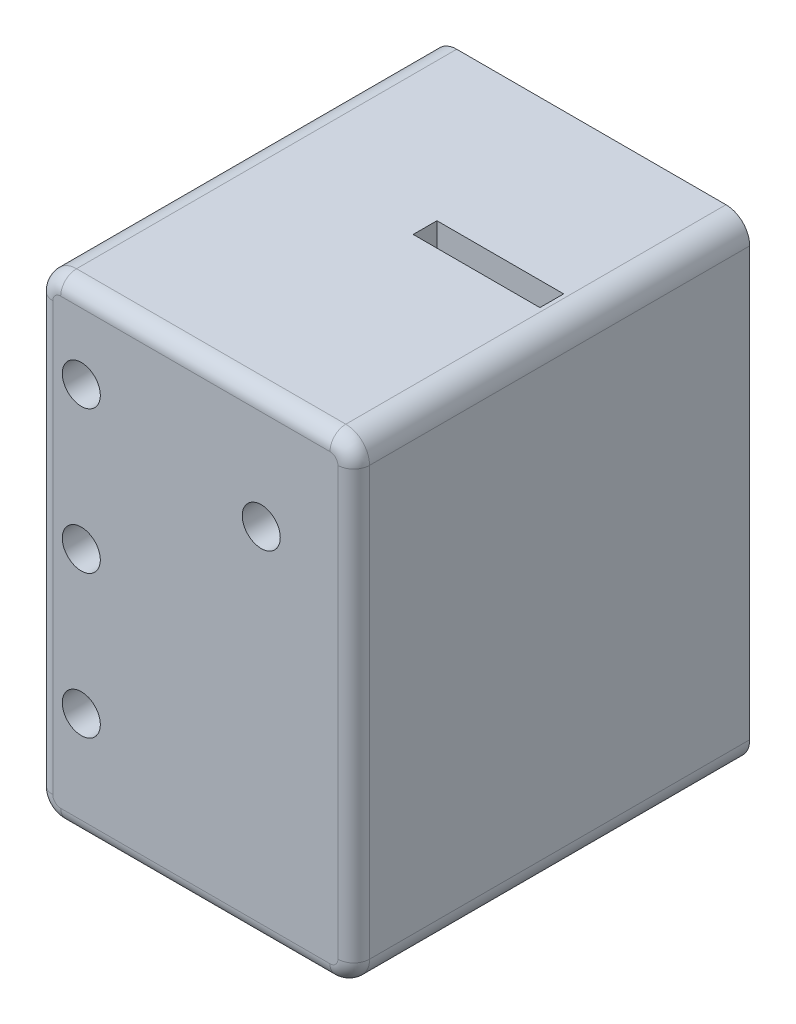
SolidWorks part; units mm, degrees
ref_plane "Front Plane" through (0, 0, 0) normal (0, 0, 1) x (1, 0, 0)
ref_plane "Top Plane" through (0, 0, 0) normal (0, 1, 0) x (1, 0, 0)
ref_plane "Right Plane" through (0, 0, 0) normal (1, 0, 0) x (0, 0, -1)
sketch "Sketch1" plane through (0, 0, 0) normal (0, 0, 1) x (1, 0, 0)
  line L0 (0, 0) -> (0, -30)
  line L1 (0, 0) -> (20, 0)
  line L2 (20, 0) -> (20, -30)
  line L3 (20, -30) -> (0, -30)
extrude "Boss-Extrude1" add sketch "Sketch1" along normal blind 25
sketch "Sketch4" plane through (0, -30, 0) normal (0, -1, 0) x (1, 0, 0)
  line L3 (18.2519, 10) -> (18.2519, 11.5)
  line L4 (18.2519, 11.5) -> (10.2519, 11.5)
  line L5 (10.2519, 11.5) -> (10.2519, 10)
  line L6 (10.2519, 10) -> (18.2519, 10)
extrude "Cut-Extrude2" cut sketch "Sketch4" against normal through all both and the other way through all contours L4 L5 L6 L3
sketch "Sketch5" plane through (0, 0, 0) normal (0, 1, 0) x (1, 0, 0)
  line L0 (18.2519, -11.5) -> (18.2519, -23)
  line L1 (18.2519, -23) -> (10.2519, -23)
  line L2 (10.2519, -23) -> (10.2519, -11.5)
  line L3 (18.2519, -11.5) -> (10.2519, -11.5) construction
  line L4 (10.2519, -11.5) -> (18.2519, -11.5)
extrude "Cut-Extrude3" cut sketch "Sketch5" against normal blind 15
sketch "Sketch6" plane through (0, -30, 0) normal (0, -1, 0) x (1, 0, 0)
  line L0 (10.2519, 10) -> (3.5878, 10)
  line L1 (3.5878, 10) -> (3.5878, 23)
  line L2 (3.5878, 23) -> (10.2519, 23)
  line L3 (10.2519, 11.5) -> (10.2519, 23) construction
  line L4 (10.2519, 23) -> (10.2519, 10)
extrude "Cut-Extrude4" cut sketch "Sketch6" against normal blind 28
sketch "Sketch7" plane through (0, 0, 10) normal (0, 0, 1) x (1, 0, 0)
  line L1 (18.2519, -15) -> (18.2519, 0) construction
  line L2 (18.2519, -12) -> (10.2519, -12)
  line L3 (10.2519, -12) -> (10.2519, -3)
  line L4 (10.2519, -3) -> (18.2519, -3)
  line L5 (18.2519, -12) -> (18.2519, -3)
extrude "Cut-Extrude5" cut sketch "Sketch7" against normal blind 3
sketch "Sketch11" plane through (0, 0, 10) normal (0, 0, 1) x (1, 0, 0)
  line L0 (10.2519, -15) -> (10.2519, -30) construction
  line L1 (3.5878, -30) -> (10.2519, -30)
  line L2 (3.5878, -30) -> (3.5878, -28)
  line L3 (3.5878, -28) -> (10.2519, -28)
  line L4 (10.2519, -30) -> (10.2519, -28)
extrude "Boss-Extrude2" add sketch "Sketch11" along direction (0, 0, -1) on the side of the normal up to surface (13 mm away) contours L4 L3 L2 L1 up to face at (10.5859, -11.75, 23)
sketch "Sketch12" plane through (0, 0, 23) normal (0, 0, -1) x (-1, 0, 0)
  line L1 (-10.2519, -2) -> (-18.2519, -2)
  line L2 (-10.2519, -2) -> (-10.2519, 0)
  line L3 (-10.2519, 0) -> (-18.2519, 0)
  line L4 (-18.2519, -2) -> (-18.2519, 0)
extrude "Boss-Extrude3" add sketch "Sketch12" along normal blind 11.5 contours L4 L3 L2 L1
sketch "Sketch13" plane through (0, 0, 0) normal (-1, 0, 0) x (0, 0, 1)
  line L1 (23, -2) -> (10, -2)
  line L2 (23, -2) -> (23, -28)
  line L3 (23, -28) -> (10, -28)
  line L4 (10, -2) -> (10, -28)
extrude "Cut-Extrude7" cut sketch "Sketch13" against normal blind 4
sketch "Sketch18" plane through (0, 0, 0) normal (0, 0, -1) x (-1, 0, 0)
  line L0 (-10.2519, 0) -> (-2.7519, 0)
  line L1 (-20, 0) -> (0, 0) construction
  circle A0 centre (-2.8, -23.1744) radius 1.2
extrude "Cut-Extrude8" cut sketch "Sketch18" against normal through all both and the other way through all contours A0
pattern_linear "LPattern1" count 3 spacing 9 along (0, 1, 0) of "Cut-Extrude8"
sketch "Sketch19" plane through (10.2519, 0, 0) normal (-1, 0, 0) x (0, 0, 1)
  line L0 (23, -28) -> (23, -2) construction
  line L1 (23, -15) -> (18.3, -15)
  line L2 (23, -15) -> (23, -28)
  line L7 (18.3, -15) -> (18.3, -28)
  line L8 (10, -28) -> (23, -28) construction
  line L9 (18.3, -28) -> (23, -28)
extrude "Boss-Extrude5" add sketch "Sketch19" along normal blind 6 contours L7 L9 L2 L1
fillet "Fillet1" radius 1.5 4 edges at (20, 0, 12.5) (0, 0, 12.5) (20, -30, 12.5) (0, -30, 12.5)
fillet "Fillet2" radius 1 1 edges at (10.2519, -21.5, 18.3)
fillet "Fillet3" radius 1 1 edges at (10.2519, -7.5, 10)
fillet "Fillet4" radius 1 1 edges at (18.2519, -8.5, 23)
fillet "Fillet5" radius 1 8 edges at (19.5607, -29.5607, 25) (10, -30, 25) (0.4393, -29.5607, 25) (0, -15, 25) (0.4393, -0.4393, 25) (10, 0, 25) (19.5607, -0.4393, 25) (20, -15, 25)
fillet "Fillet6" radius 1 2 edges at (10.2519, -7.5, 7) (18.2519, -7.5, 7)
fillet "Fillet7" radius 1 3 edges at (18.2519, -15, 16.75) (17.959, -15, 22.7071) (10.7519, -15, 23)
fillet "Fillet8" radius 1 3 edges at (18.2519, -2, 16.75) (17.959, -2, 22.7071) (8.6259, -2, 23)
fillet "Fillet9" radius 1 2 edges at (4.2519, -14.7071, 22.7071) (4.2519, -15, 20.15)
fillet "Fillet11" radius 1 1 edges at (4.2519, -28, 20.65)
sketch "Sketch20" plane through (0, 0, 25) normal (0, 0, 1) x (1, 0, 0)
  circle A0 centre (14.1613, -7.2695) radius 1.2
extrude "Cut-Extrude9" cut sketch "Sketch20" against normal through all contours A0
